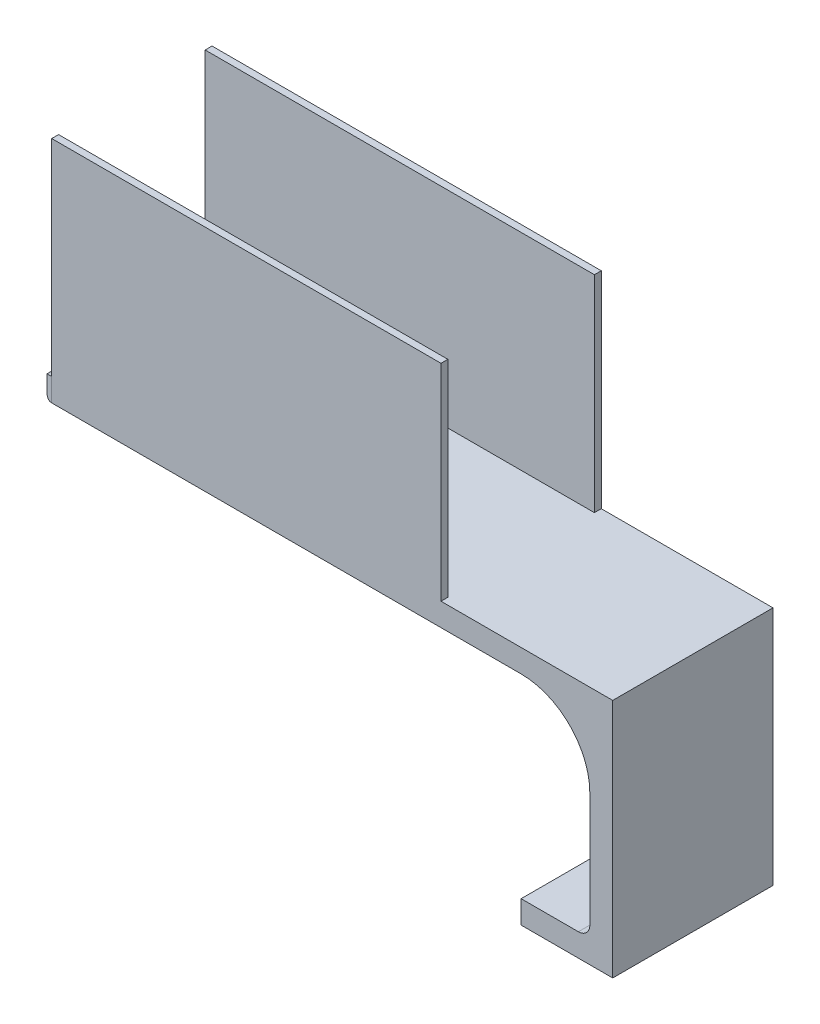
SolidWorks part; units mm, degrees
ref_plane "Front Plane" through (0, 0, 0) normal (0, 0, 1) x (1, 0, 0)
ref_plane "Top Plane" through (0, 0, 0) normal (0, 1, 0) x (1, 0, 0)
ref_plane "Right Plane" through (0, 0, 0) normal (1, 0, 0) x (0, 0, -1)
sketch "Sketch1" plane through (0, 0, 0) normal (0, 0, 1) x (1, 0, 0)
  line L0 (0, 0) -> (8, 0)
  line L1 (8, 0) -> (8, 21)
  line L2 (8, 21) -> (-42, 21)
  line L3 (-42, 21) -> (-42, 19)
  line L4 (-42, 19) -> (6, 19)
  line L5 (6, 19) -> (6, 2)
  line L6 (6, 2) -> (0, 2)
  line L7 (0, 2) -> (0, 0)
  dimension "D1" = 2
  dimension "D2" = 8
  dimension "D3" = 6
  dimension "D4" = 21
  dimension "D5" = 50
  dimension "D6" = 17
extrude "Boss-Extrude1" add sketch "Sketch1" along normal blind 14
fillet "Fillet1" radius 1 5 edges at (-42, 21, 7) (-42, 20, 14) (-42, 19, 7) (-42, 20, 0) (6, 2, 7)
sketch "Sketch2" plane through (6, 0, 0) normal (-1, 0, 0) x (0, 0, 1)
  text T0 "MICO" font "Poppins ExtraBold" height 3
extrude "Boss-Extrude2" add sketch "Sketch2" along normal blind 0.8
sketch "Sketch4" plane through (0, 21, 0) normal (0, 1, 0) x (1, 0, 0)
  line L3 (8, -14) -> (-41, -14) construction
  line L4 (-41, 0) -> (-7, 0)
  line L5 (-41, 0) -> (-41, -0.6)
  line L6 (-41, -14) -> (-7, -14)
  line L7 (-7, 0) -> (-7, -0.6)
  line L8 (-41, -13.4) -> (-41, -14)
  line L9 (-41, -0.6) -> (-7, -0.6)
  line L11 (-41, -13.4) -> (-7, -13.4)
  line L13 (-7, -13.4) -> (-7, -14)
  dimension "D1" = 34
  dimension "D2" = 14
  dimension "D3" = 0.6
  dimension "D4" = 0.6
  dimension "D5" = 14
  dimension "D6" = 12.8
extrude "Boss-Extrude3" add sketch "Sketch4" along normal blind 18
fillet "Fillet2" radius 6 1 edges at (6, 19, 7)
